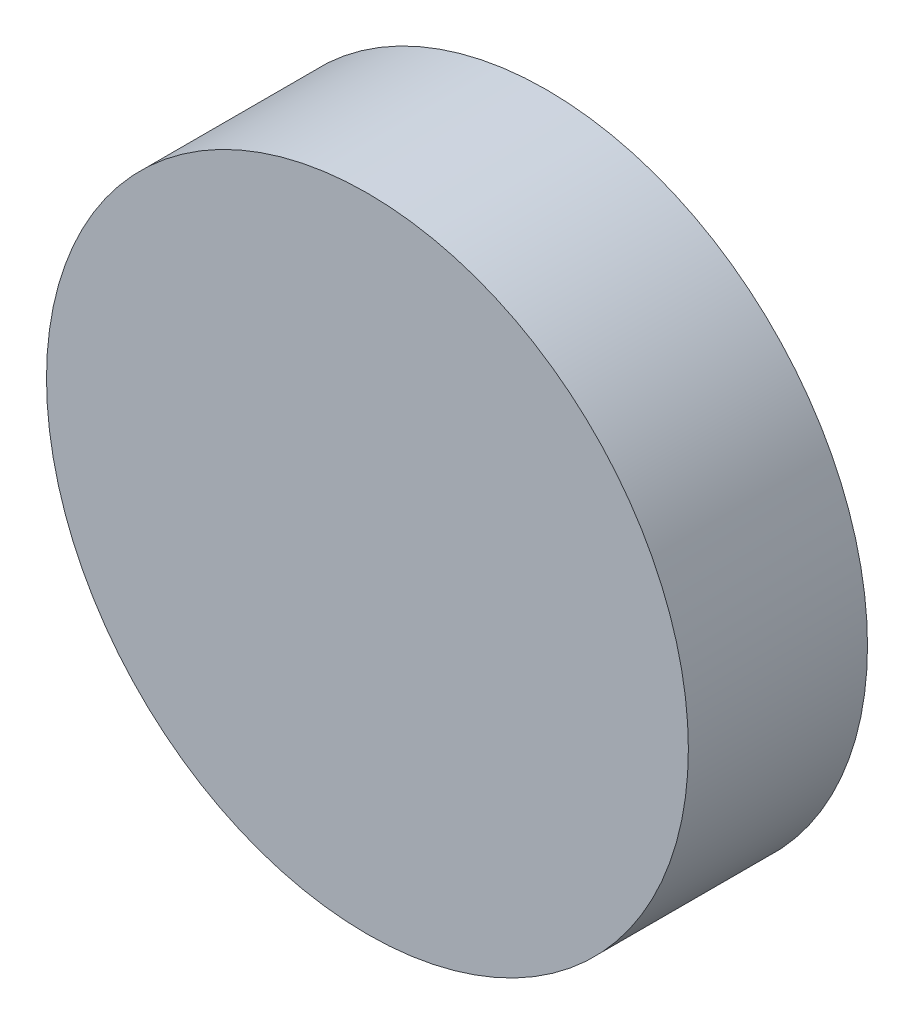
SolidWorks part; units mm, degrees
ref_plane "Plan de face" through (0, 0, 0) normal (0, 0, 1) x (1, 0, 0)
ref_plane "Plan de dessus" through (0, 0, 0) normal (0, 1, 0) x (1, 0, 0)
ref_plane "Plan de droite" through (0, 0, 0) normal (1, 0, 0) x (0, 0, -1)
sketch "Esquisse1" plane through (0, 0, 0) normal (0, 0, 1) x (1, 0, 0)
  circle A0 centre (0, 0) radius 10.75
  dimension "D1" = 21.5
extrude "Boss.-Extru.1" add sketch "Esquisse1" along normal blind 6
sketch "Esquisse3" plane through (0, 0, 0) normal (0, 0, -1) x (-1, 0, 0)
  line L0 (0, 0) -> (0, 4.0852) construction
  circle A0 centre (-2.5, 0) radius 0.7
  circle A1 centre (2.5, 0) radius 0.7
  dimension "D1" = 1.4
  dimension "D2" = 1.4
  dimension "D3" = 5
extrude "Boss.-Extru.2" add sketch "Esquisse3" along normal blind 3
